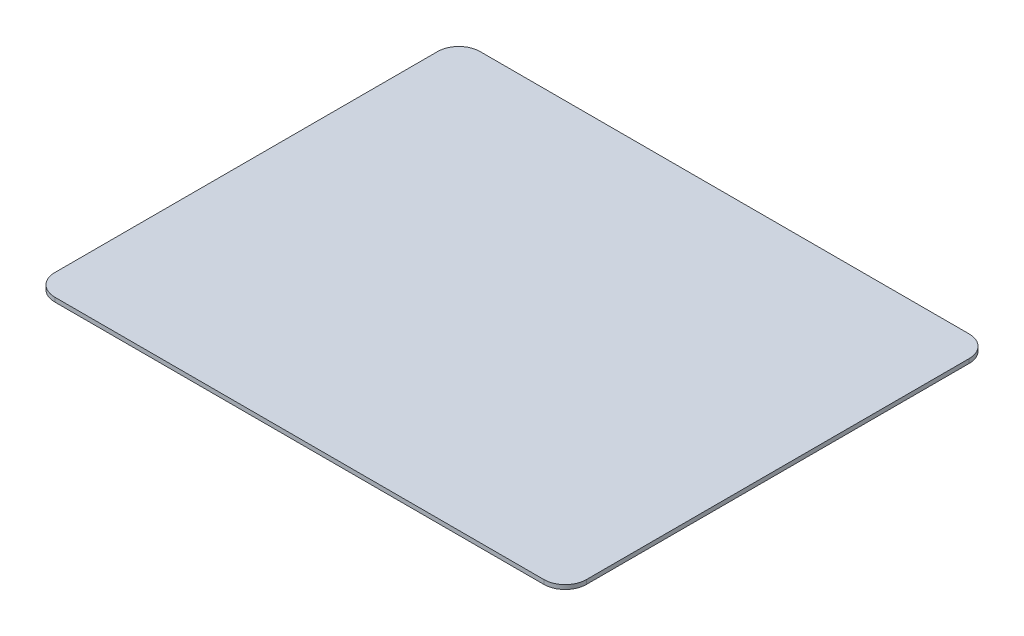
SolidWorks part; units mm, degrees
ref_plane "Front" through (0, 0, 0) normal (0, 0, 1) x (1, 0, 0)
ref_plane "Top" through (0, 0, 0) normal (0, 1, 0) x (1, 0, 0)
ref_plane "Right" through (0, 0, 0) normal (1, 0, 0) x (0, 0, -1)
sketch "Esboço1" plane through (0, 0, 0) normal (0, 1, 0) x (1, 0, 0)
  line L1 (-115, -100) -> (115, -100)
  line L2 (-125, -90) -> (-125, 90)
  line L3 (-115, 100) -> (115, 100)
  line L4 (125, -90) -> (125, 90)
  line L5 (-125, -100) -> (125, 100) construction
  line L6 (-125, 100) -> (125, -100) construction
  arc A0 (-125, 90) -> (-115, 100) centre (-115, 90) cw
  arc A1 (115, 100) -> (125, 90) centre (115, 90) cw
  arc A2 (115, -100) -> (125, -90) centre (115, -90) ccw
  arc A3 (-115, -100) -> (-125, -90) centre (-115, -90) cw
  point P0 (0, 0)
  dimension "D3" = 10
  dimension "D1" = 250
  dimension "D2" = 200
base flange "Flange-base1" sketch "Esboço1" thickness 2 reverse thickness direction no parameters "D1"=0.5
sketch "Curva-Linhas1" [suppressed] plane through (0, 0, 0) normal (0, 1, 0) x (1, 0, 0)
sketch "Caixa delimitadora1" [suppressed] plane through (0, 0, 0) normal (0, 1, 0) x (1, 0, 0)
sheet metal parameters "Chapa metálica1" thickness 2 parameters "D1"=0.5
flat pattern "Padrão-Plano1" [suppressed]
sketch "Curva-Linhas2" plane through (0, 0, 0) normal (0, 1, 0) x (1, 0, 0)
sketch3d "Caixa delimitadora2" [suppressed]
  line L0 (10, 10, 0) -> (-240, 10, 0) construction
  line L1 (10, -190, 0) -> (-240, -190, 0) construction
  line L2 (10, 10, 0) -> (10, -190, 0) construction
  line L3 (-240, 10, 0) -> (-240, -190, 0) construction
